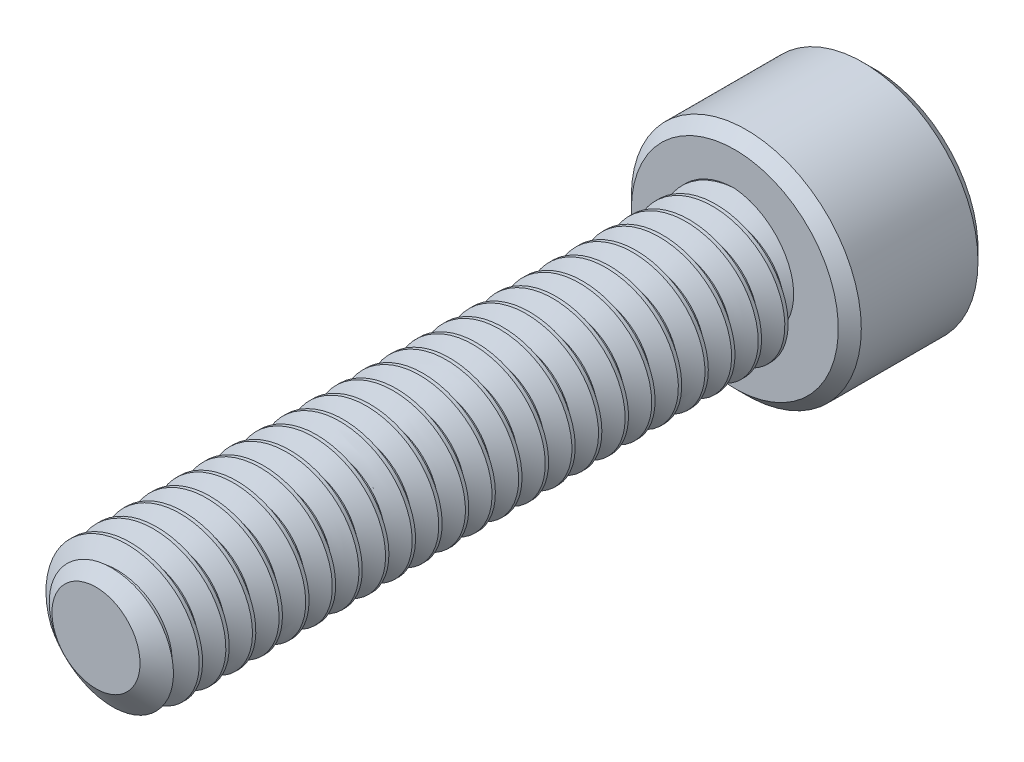
SolidWorks part; units mm, degrees
other "DetailItem1"
ref_plane "Front Plane" through (0, 0, 0) normal (0, 0, 1) x (1, 0, 0)
ref_plane "Top Plane" through (0, 0, 0) normal (0, 1, 0) x (1, 0, 0)
ref_plane "Right Plane" through (0, 0, 0) normal (1, 0, 0) x (0, 0, -1)
sketch "Sketch1" plane through (0, 0, 0) normal (0, 0, 1) x (1, 0, 0)
  circle A0 centre (0, 0) radius 2.0828
  dimension "OD" = 4.1656
extrude "Extrude1" add sketch "Sketch1" against normal blind 19.05
sketch "Sketch2" plane through (0, 0, 0) normal (0, 0, 1) x (1, 0, 0)
  circle A0 centre (0, 0) radius 2.0828 construction
  circle A1 centre (0, 0) radius 2.0828
curve "Helix/Spiral1" pitch 0.7937 height 19.8438 turns 25 parameters "pitch"=0.7937
sketch "Sketch3" plane through (0, 0, 0) normal (1, 0, 0) x (0, 0, -1)
  line L0 (-0.6945, 2.0828) -> (-0.3969, 1.5672)
  line L1 (-0.3969, 1.5672) -> (-0.2977, 1.5672)
  line L2 (-0.2977, 1.5672) -> (0, 2.0828)
  line L3 (-0.6945, 2.0828) -> (0, 2.0828)
  line L4 (-0.3473, 2.0828) -> (-0.3473, 1.5672) construction
  line L5 (-0.5457, 1.825) -> (-0.1488, 1.825) construction
  line L6 (0, 2.0828) -> (0, -2.0828) construction
  dimension "D1" = 0.0992
  dimension "D2" = 0.3969
  dimension "D3" = 60
sweep "Cut-Sweep1" cut profiles "Sketch3" path "Helix/Spiral1"
sketch "Sketch4" plane through (0, 0, 0) normal (1, 0, 0) x (0, 0, -1)
  line L0 (0.5388, 2.0828) -> (0, 1.3132)
  line L1 (0, 1.3132) -> (0, 2.0828)
  line L2 (0.5388, 2.0828) -> (0, 2.0828)
  line L3 (-0.6945, 2.0828) -> (0, 2.0828) construction
  line L4 (0, 0) -> (7.0209, 0) construction
  dimension "D1" = 55
  dimension "D2" = 0.254
revolve "Cut-Revolve1" cut sketch "Sketch4" angle 360 about L4
sketch "Sketch5" plane through (0, 0, 0) normal (1, 0, 0) x (0, 0, -1)
  line L0 (19.05, -1.5805) -> (19.05, 1.4861) construction
  line L1 (19.05, 2.2098) -> (0.1202, 2.2098)
  line L2 (19.05, 2.2098) -> (19.05, 0)
  line L3 (19.05, 0) -> (0, 0)
  line L4 (0, 1.8796) -> (0, 0)
  line L5 (0.1202, 2.2098) -> (0, 1.8796)
  line L6 (0, 0) -> (9.9695, 0) construction
  point P3 (0, 2.2098)
  point P10 (0, 2.2098)
  dimension "D1" = 0.3302
  dimension "D2" = 0.127
  dimension "D3" = 20
  dimension "Min Thread" = 0
revolve "partially thread" [suppressed] add sketch "Sketch5" angle 360 about L6
sketch "Sketch6" plane through (0, 0, -19.05) normal (0, 0, -1) x (-1, 0, 0)
  circle A0 centre (0, 0) radius 3.429
  dimension "head dia" = 6.858
extrude "Extrude2" add sketch "Sketch6" along normal blind 4.1656
sketch "Sketch7" plane through (0, 0, -23.2156) normal (0, 0, -1) x (-1, 0, 0)
  line L1 (0, 2.0622) -> (-1.7859, 1.0311)
  line L2 (-1.7859, 1.0311) -> (-1.7859, -1.0311)
  line L3 (-1.7859, -1.0311) -> (0, -2.0622)
  line L4 (0, -2.0622) -> (1.7859, -1.0311)
  line L5 (1.7859, -1.0311) -> (1.7859, 1.0311)
  line L6 (1.7859, 1.0311) -> (0, 2.0622)
  circle A0 centre (0, 0) radius 1.7859 construction
  dimension "hex dia" = 3.5719
extrude "Cut-Extrude1" cut sketch "Sketch7" against normal blind 2.6789
sketch "Sketch8" plane through (0, 0, -23.2156) normal (0, 0, -1) x (-1, 0, 0)
  circle A0 centre (0, 0) radius 2.0622
extrude "Cut-Extrude2" cut sketch "Sketch8" against normal through all draft 45
chamfer "Chamfer1" distance 0.3429 angle 45 2 edges at (-3.429, 0, -23.2156) (-3.429, 0, -19.05)
sketch "Sketch9" plane through (0, 0, 0) normal (1, 0, 0) x (0, 0, -1)
  line L0 (0, 2.0828) -> (0, -2.0828) construction
  line L1 (1.9844, 2.0828) -> (1.9844, -2.0828) construction
  dimension "D1" = 1.9844
equation "\"D3@Helix/Spiral1\" = \"screw length@Extrude1\"+\"pitch@Helix/Spiral1\""
equation "\"D1@Sketch3\" = \"pitch@Helix/Spiral1\"*.125"
equation "\"D2@Sketch3\" = \"pitch@Helix/Spiral1\"*.5"
equation "\"D1@Cut-Extrude1\" = \"hex dia@Sketch7\"*.75"
equation "\"D1@Chamfer1\" = \"head dia@Sketch6\"*.05"
equation "\"D1@Sketch9\" = \"pitch@Helix/Spiral1\"*2.5"
